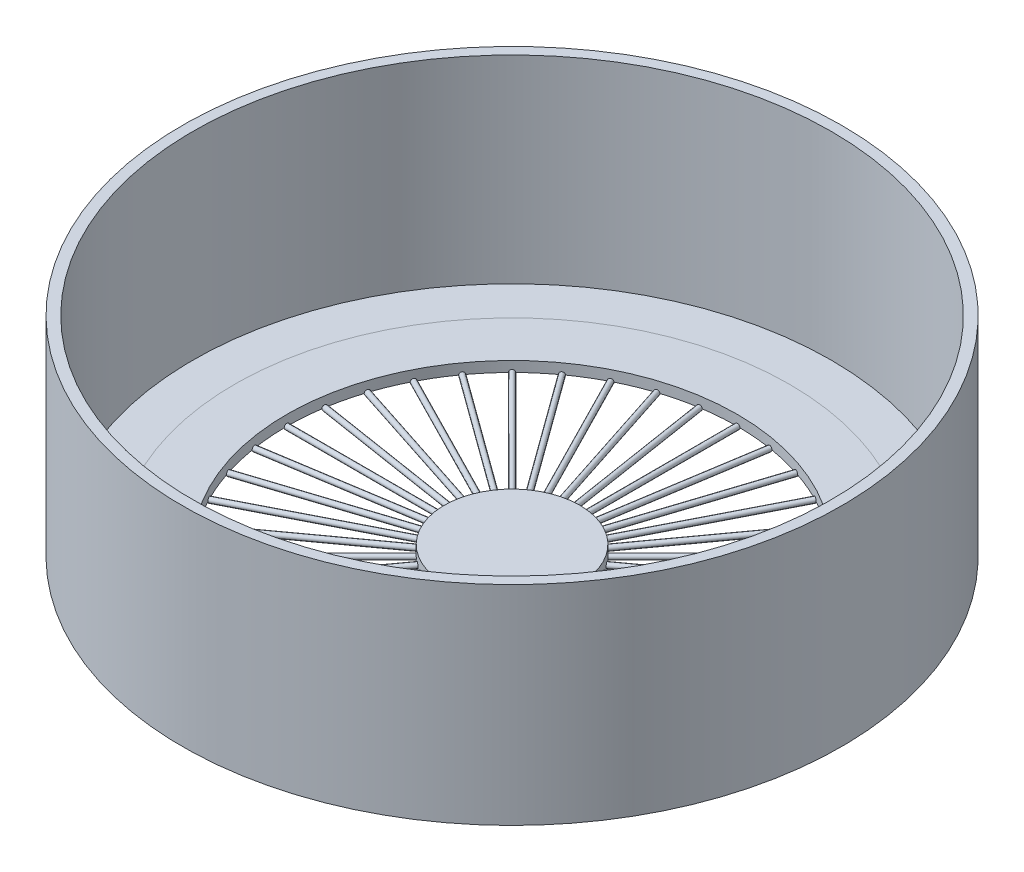
SolidWorks part; units mm, degrees
ref_plane "Front Plane" through (0, 0, 0) normal (0, 0, 1) x (1, 0, 0)
ref_plane "Top Plane" through (0, 0, 0) normal (0, 1, 0) x (1, 0, 0)
ref_plane "Right Plane" through (0, 0, 0) normal (1, 0, 0) x (0, 0, -1)
sketch "Sketch1" plane through (0, 0, 0) normal (0, 0, 1) x (1, 0, 0)
  line L0 (266, 0) -> (316, 0.0391)
  line L1 (316, 0.0391) -> (316, 200.0391)
  line L2 (266, 0) -> (216, 0)
  line L3 (306, 10.0313) -> (306, 200.0391)
  line L4 (265.9961, 10) -> (306, 10.0313)
  line L5 (265.9961, 10) -> (216, 10)
  line L6 (216, 10) -> (216, 0)
  line L7 (316, 200.0391) -> (306, 200.0391)
  line L8 (0, 0) -> (0, 92.0741) construction
  dimension "D1" = 200
  dimension "D2" = 50
  dimension "D3" = 316
  dimension "D4" = 50
  dimension "D5" = 10
revolve "Revolve1" add sketch "Sketch1" angle 360 about L8
sketch "Sketch2" plane through (0, 0, 0) normal (0, -1, 0) x (-1, 0, 0)
  line L0 (0, -216) -> (0, 216)
  line L1 (40, -212.264) -> (40, 212.264)
  line L2 (80, -200.639) -> (80, 200.639)
  line L3 (120, -179.5996) -> (120, 179.5996)
  line L4 (150, -155.422) -> (150, 155.422)
  line L5 (-40, -212.264) -> (-40, 212.264)
  line L6 (-80, -200.639) -> (-80, 200.639)
  line L7 (-120, -179.5996) -> (-120, 179.5996)
  line L8 (-150, -155.422) -> (-150, 155.422)
  line L9 (40, -212.264) -> (-40, -212.264)
  line L10 (80, -200.639) -> (-80, -200.639)
  line L11 (120, -179.5996) -> (-120, -179.5996)
  line L12 (-150, -155.422) -> (150, -155.422)
  line L13 (0, 0) -> (57.3912, 0) construction
  line L14 (40, 212.264) -> (-40, 212.264)
  line L15 (80, 200.639) -> (-80, 200.639)
  line L16 (120, 179.5996) -> (-120, 179.5996)
  line L17 (-150, 155.422) -> (150, 155.422)
  line L19 (216, 0) -> (-216, 0)
  circle A0 centre (0, 0) radius 216 construction
  dimension "D1" = 40
  dimension "D2" = 40
  dimension "D3" = 40
  dimension "D4" = 30
sweep "Sweep1" add path "Sketch2" circular profile diameter 5 parameters "D3"=5
pattern_circular "CirPattern1" count 40 over 360 about axis through (0, 0, 0) along (0, -1, 0) of "Sweep1"
sketch "Sketch46" plane through (0, 0, 0) normal (0, -1, 0) x (1, 0, 0)
  circle A1 centre (0, 0) radius 65
  dimension "D1" = 130
extrude "Boss-Extrude1" add sketch "Sketch46" against normal blind 10
sketch "Sketch47" plane through (0, 0, 0) normal (0, -1, 0) x (1, 0, 0)
  circle A0 centre (0, 0) radius 65
extrude "Boss-Extrude2" add sketch "Sketch47" along normal blind 10
scale "Echelle1" scale about centroid uniform scaling yes scale factor 0.47
